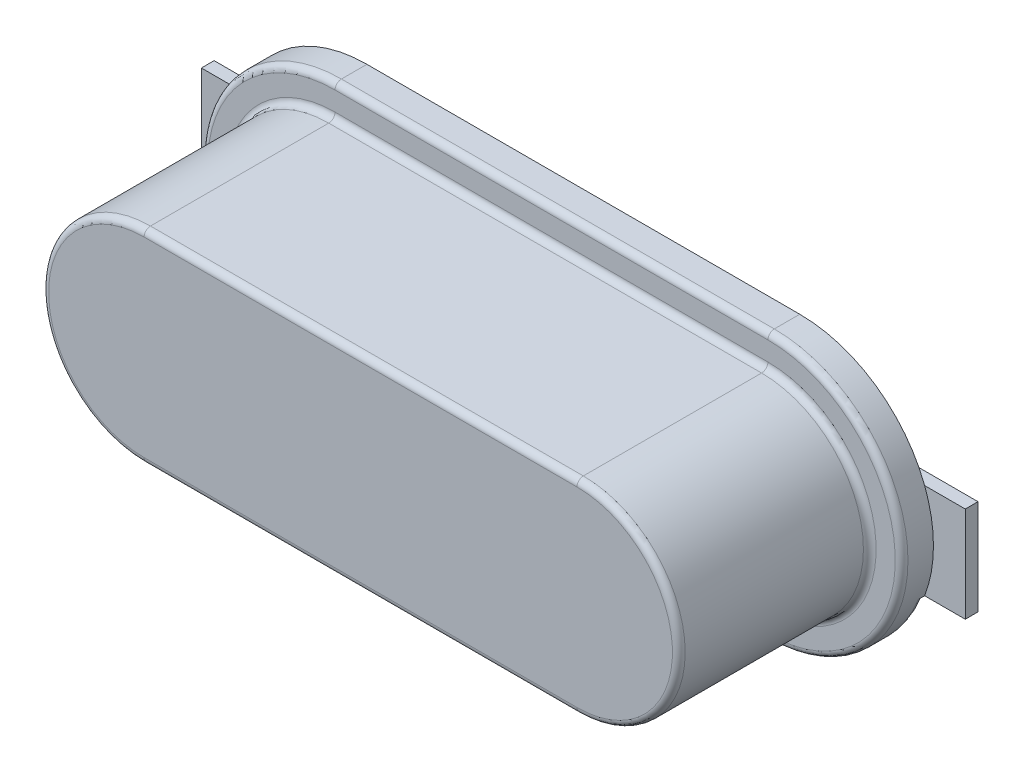
SolidWorks part; units mm, degrees
ref_plane "前视基准面" through (0, 0, 0) normal (0, 0, 1) x (1, 0, 0)
ref_plane "上视基准面" through (0, 0, 0) normal (0, 1, 0) x (1, 0, 0)
ref_plane "右视基准面" through (0, 0, 0) normal (1, 0, 0) x (0, 0, -1)
sketch "草图1" plane through (0, 0, 0) normal (0, 0, 1) x (1, 0, 0)
  line L0 (-1000, 0) -> (49000, 0) construction
  line L1 (0, -1000) -> (0, 49000) construction
  line L2 (3.4, 2.1) -> (-3.4, 2.1)
  line L3 (3.4, -2.1) -> (-3.4, -2.1)
  arc A0 (3.4, -2.1) -> (3.4, 2.1) centre (3.4, 0) ccw
  arc A1 (-3.4, -2.1) -> (-3.4, 2.1) centre (-3.4, 0) cw
  point P10 (0, 2.1)
  point P13 (0, -2.1)
  dimension "D1" = 4.2
  dimension "D2" = 6.8
extrude "凸台-拉伸1" add sketch "草图1" along normal blind 0.5
sketch "草图2" plane through (0, 0, 0.5) normal (0, 0, 1) x (1, 0, 0)
  line L0 (-1000, 0) -> (49000, 0) construction
  line L1 (0, -1000) -> (0, 49000) construction
  line L2 (-3.4, 1.6) -> (3.4, 1.6)
  line L3 (-3.4, -1.6) -> (3.4, -1.6)
  arc A0 (3.4, -1.6) -> (3.4, 1.6) centre (3.4, 0) ccw
  arc A1 (-3.4, -1.6) -> (-3.4, 1.6) centre (-3.4, 0) cw
  point P10 (0, -1.6)
  point P13 (0, 1.6)
  dimension "D2" = 6.8
  dimension "D3" = 3.2
  dimension "D1" = 3.2
extrude "凸台-拉伸2" add sketch "草图2" along normal blind 3
sketch "草图3" plane through (0, 0, 0) normal (0, 0, -1) x (-1, 0, 0)
  line L0 (-6, 0) -> (0, 0) construction
  line L1 (0, -1000) -> (0, 49000) construction
  line L2 (-2.5, 0.75) -> (-2.5, -0.75)
  line L3 (2.5, 0.75) -> (2.5, -0.75)
  line L4 (-6, 0.75) -> (-2.5, 0.75)
  line L5 (-6, -0.75) -> (-2.5, -0.75)
  line L6 (-6, 0.75) -> (-6, -0.75)
  line L7 (6, 0.75) -> (6, -0.75)
  line L8 (6, -0.75) -> (2.5, -0.75)
  line L9 (6, 0.75) -> (2.5, 0.75)
  dimension "D1" = 2.5
  dimension "D2" = 1.5
  dimension "D3" = 3.5
extrude "凸台-拉伸3" add sketch "草图3" along normal blind 0.2
fillet "圆角1" radius 0.1 15 edges at (4.5906, -1.7299, 0) (-5.5, 0, 0.5) (0, 2.1, 0.5) (5.5, 0, 0.5) (-5, 0, 0.5) (0, 1.6, 0.5) (5, 0, 0.5) (0, 1.6, 3.5) (5, 0, 3.5) (0, -2.1, 0) (0, -2.1, 0.5) (0, -1.6, 0.5) (-5, 0, 3.5) (0, -1.6, 3.5) (-4.5906, -1.7299, 0)
